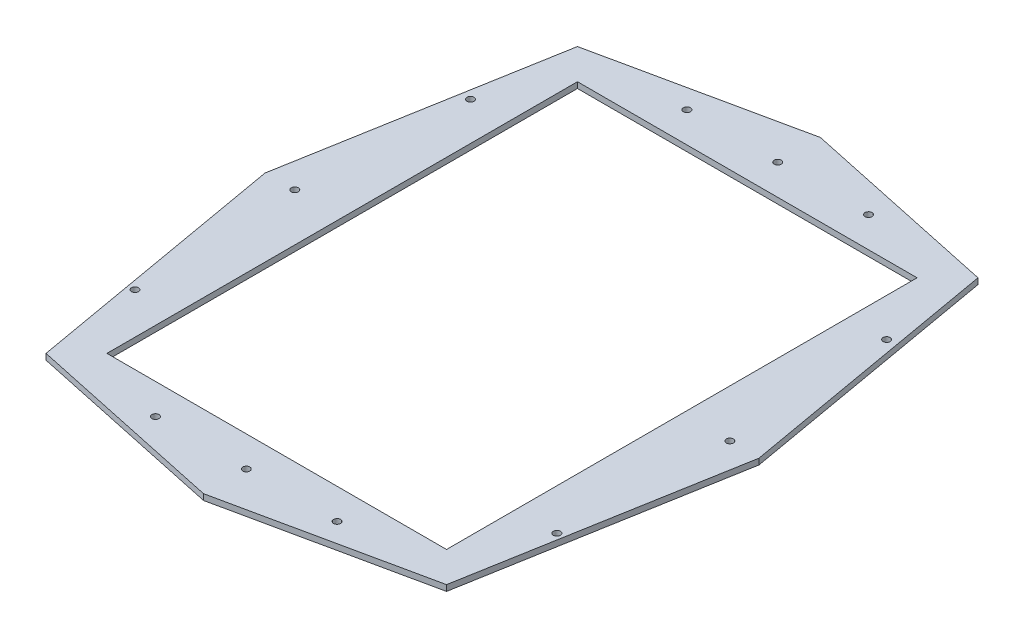
SolidWorks part; units mm, degrees
ref_plane "Front Plane" through (0, 0, 0) normal (0, 0, 1) x (1, 0, 0)
ref_plane "Top Plane" through (0, 0, 0) normal (0, 1, 0) x (1, 0, 0)
ref_plane "Right Plane" through (0, 0, 0) normal (1, 0, 0) x (0, 0, -1)
sketch "Sketch1" plane through (0, -125.1639, 0) normal (0, -1, 0) x (-1, 0, 0)
  line L39 (0, 165.5699) -> (-107.5, 142.6399) construction
  line L40 (-107.5, 142.6399) -> (-132.5632, 0) construction
  line L41 (-132.5632, 0) -> (-107.5, -142.6399) construction
  line L42 (-107.5, -142.6399) -> (0, -165.5699) construction
  line L47 (0, -165.5699) -> (107.5, -142.6399) construction
  line L48 (107.5, -142.6399) -> (132.5632, 0) construction
  line L49 (132.5632, 0) -> (107.5, 142.6399) construction
  line L50 (107.5, 142.6399) -> (0, 165.5699) construction
  line L51 (-107.5, 142.6399) -> (-132.5632, 0)
  line L52 (-132.5632, 0) -> (-107.5, -142.6399)
  line L53 (-107.5, -142.6399) -> (0, -165.5699)
  line L54 (0, -165.5699) -> (107.5, -142.6399)
  line L55 (107.5, -142.6399) -> (132.5632, 0)
  line L56 (132.5632, 0) -> (107.5, 142.6399)
  line L57 (107.5, 142.6399) -> (0, 165.5699)
  line L58 (0, 165.5699) -> (-107.5, 142.6399)
  line L82 (-97.5, -132.6399) -> (97.5, -132.6399) construction
  line L83 (-91.15, 126.2899) -> (91.15, 126.2899)
  line L84 (-91.15, 126.2899) -> (-91.15, -126.2899)
  line L85 (-91.15, -126.2899) -> (91.15, -126.2899)
  line L86 (91.15, 126.2899) -> (91.15, -126.2899)
  line L87 (-91.15, 126.2899) -> (91.15, -126.2899) construction
  line L88 (-91.15, -126.2899) -> (91.15, 126.2899) construction
  line L89 (-97.5, -132.6399) -> (-97.5, 132.6399) construction
  circle A0 centre (-111.6902, 89.4108) radius 1.8987 construction
  circle A1 centre (-116.75, 0.1657) radius 1.8987 construction
  circle A2 centre (-113.2269, -89.1534) radius 1.8987 construction
  circle A3 centre (-48.75, -142.6399) radius 1.8987 construction
  circle A4 centre (0, -142.6399) radius 1.8987 construction
  circle A5 centre (48.75, -142.6399) radius 1.8987 construction
  circle A6 centre (113.2269, -89.1534) radius 1.8692 construction
  circle A7 centre (116.75, 0.1657) radius 1.8986 construction
  circle A8 centre (111.6902, 89.4108) radius 1.8987 construction
  circle A9 centre (48.75, 142.6399) radius 1.8987 construction
  circle A10 centre (0, 142.6399) radius 1.8987 construction
  circle A11 centre (-48.75, 142.6399) radius 1.8987 construction
  circle A12 centre (-111.6902, 89.4108) radius 1.8987
  circle A13 centre (-116.75, 0.1657) radius 1.8987
  circle A14 centre (-113.2269, -89.1534) radius 1.8987
  circle A15 centre (-48.75, -142.6399) radius 1.8987
  circle A16 centre (0, -142.6399) radius 1.8987
  circle A17 centre (48.75, -142.6399) radius 1.8987
  circle A18 centre (113.2269, -89.1534) radius 1.8692
  circle A19 centre (116.75, 0.1657) radius 1.8987
  circle A20 centre (111.6902, 89.4108) radius 1.8987
  circle A21 centre (48.75, 142.6399) radius 1.8987
  circle A22 centre (0, 142.6399) radius 1.8987
  circle A23 centre (-48.75, 142.6399) radius 1.8987
  point P4 (0, 0)
  dimension "D1" = 6.35
  dimension "D2" = 6.35
extrude "Boss-Extrude1" add sketch "Sketch1" along normal blind 3.175
